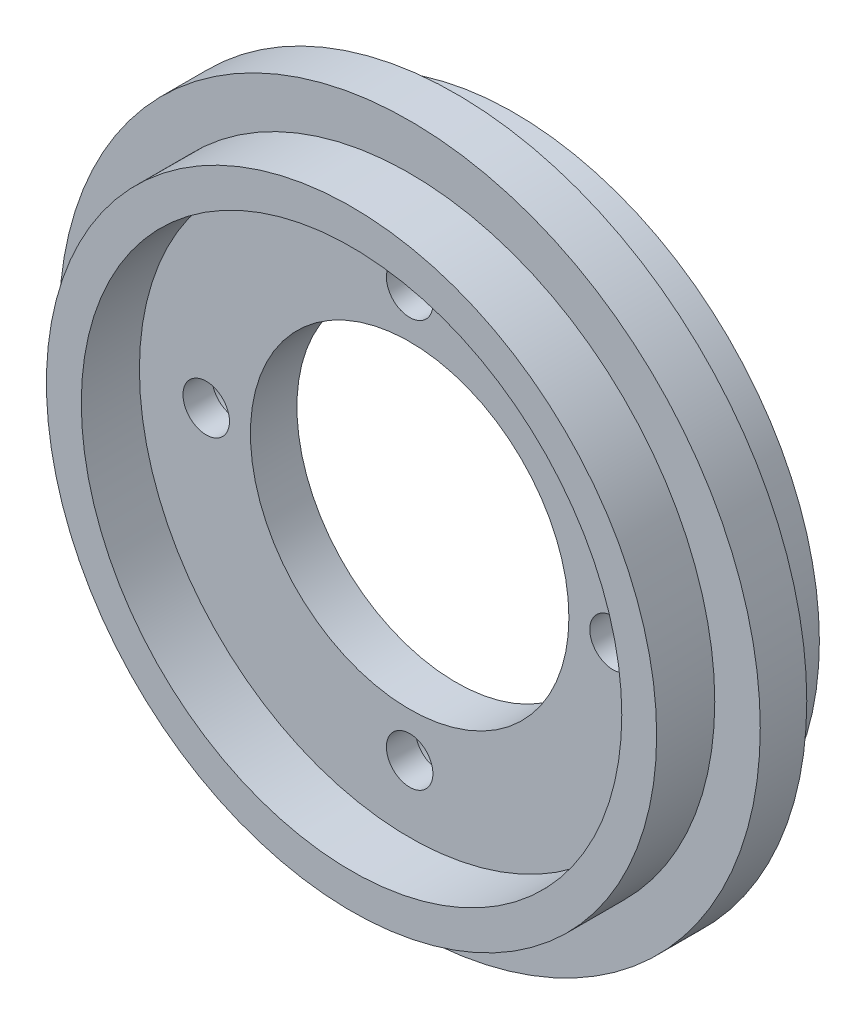
SolidWorks part; units mm, degrees
ref_plane "Alzado" through (0, 0, 0) normal (0, 0, 1) x (1, 0, 0)
ref_plane "Planta" through (0, 0, 0) normal (0, 1, 0) x (1, 0, 0)
ref_plane "Vista lateral" through (0, 0, 0) normal (1, 0, 0) x (0, 0, -1)
sketch "Croquis1" plane through (0, 0, 0) normal (0, 0, 1) x (1, 0, 0)
  circle A0 centre (0, 0) radius 30.165
  circle A1 centre (0, 0) radius 13.7
  circle A2 centre (0, 0) radius 17.5 construction
  circle A3 centre (0, 17.5) radius 2
  circle A4 centre (17.5, 0) radius 2
  circle A5 centre (-17.5, 0) radius 2
  circle A6 centre (0, -17.5) radius 2
  dimension "D1" = 60.33
  dimension "D2" = 27.4
  dimension "D3" = 35
  dimension "D4" = 4
  dimension "D5" = 4
  dimension "D6" = 4
  dimension "D7" = 4
extrude "Saliente-Extruir1" add sketch "Croquis1" along normal blind 2 and the other way blind 2
sketch "Croquis3" plane through (0, 0, 2) normal (0, 0, 1) x (1, 0, 0)
  circle A0 centre (0, 0) radius 26.25
  circle A1 centre (0, 0) radius 23.25
  dimension "D1" = 52.5
  dimension "D2" = 3
extrude "Saliente-Extruir2" add sketch "Croquis3" along normal blind 5
sketch "Croquis4" plane through (0, 0, -2) normal (0, 0, -1) x (-1, 0, 0)
  circle A0 centre (0, 17.5) radius 3.5
  circle A1 centre (17.5, 0) radius 3.5
  circle A2 centre (-17.5, 0) radius 3.5
  circle A3 centre (0, -17.5) radius 3.5
  dimension "D1" = 7
  dimension "D2" = 7
  dimension "D3" = 7
  dimension "D4" = 7
extrude "Cortar-Extruir1" cut sketch "Croquis4" against normal blind 1.5
mirror "Simetría1" about plane through (0, 0, 0) normal (0, 0, 1) of "Saliente-Extruir2"
